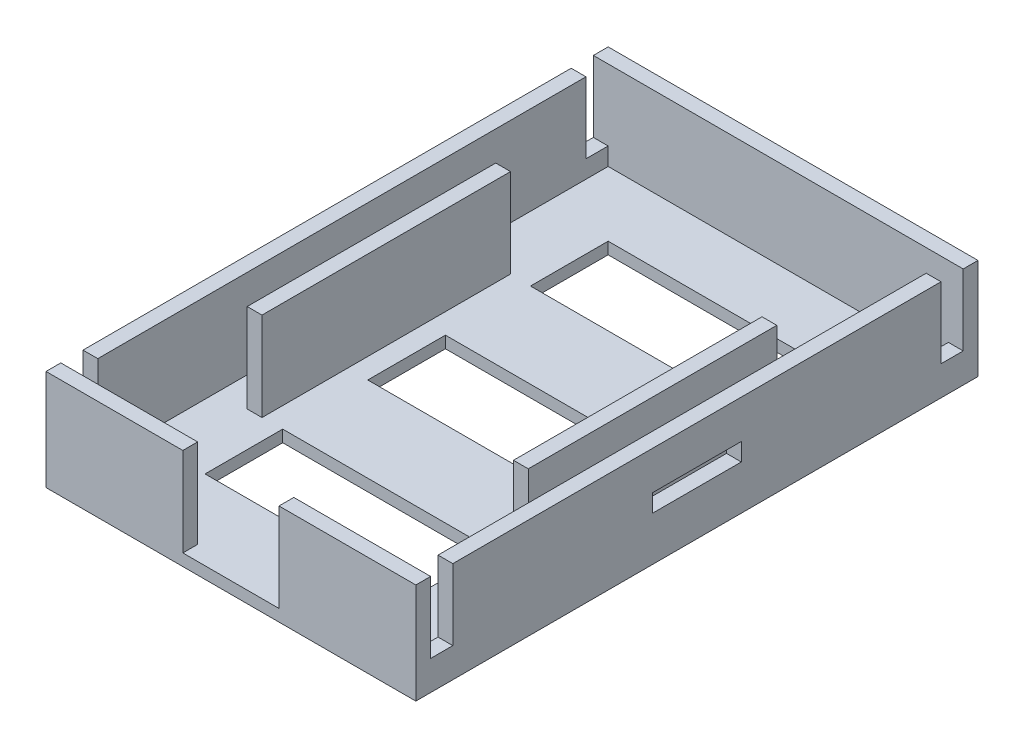
SolidWorks part; units mm, degrees
ref_plane "Front Plane" through (0, 0, 0) normal (0, 0, 1) x (1, 0, 0)
ref_plane "Top Plane" through (0, 0, 0) normal (0, 1, 0) x (1, 0, 0)
ref_plane "Right Plane" through (0, 0, 0) normal (1, 0, 0) x (0, 0, -1)
sketch "Sketch1" plane through (0, 0, 0) normal (0, 1, 0) x (1, 0, 0)
  line L1 (-12.5, -19) -> (12.5, -19)
  line L2 (-12.5, -19) -> (-12.5, 19)
  line L3 (-12.5, 19) -> (12.5, 19)
  line L4 (12.5, -19) -> (12.5, 19)
  line L5 (-12.5, -19) -> (12.5, 19) construction
  line L6 (-12.5, 19) -> (12.5, -19) construction
  point P0 (0, 0)
  dimension "D1" = 25
  dimension "D2" = 38
extrude "Boss-Extrude1" add sketch "Sketch1" along normal blind 6.8
sketch "Sketch2" plane through (0, 6.8, 0) normal (0, 1, 0) x (1, 0, 0)
  line L0 (-12.5, 19) -> (-12.5, -19) construction
  line L1 (-11.5, -18) -> (11.5, -18)
  line L2 (-11.5, -18) -> (-11.5, 18)
  line L3 (-11.5, 18) -> (11.5, 18)
  line L4 (11.5, -18) -> (11.5, 18)
  line L5 (-11.5, -18) -> (11.5, 18) construction
  line L6 (-11.5, 18) -> (11.5, -18) construction
  line L7 (-11.5, 18) -> (-12.5, 18)
  line L8 (-11.5, 18) -> (-11.5, 16.5)
  line L9 (-11.5, 16.5) -> (-12.5, 16.5)
  line L10 (-12.5, 18) -> (-12.5, 16.5)
  line L11 (0, -55) -> (0, 55) construction
  line L12 (11.5, 16.5) -> (12.5, 16.5)
  line L13 (12.5, 18) -> (12.5, 16.5)
  line L14 (11.5, 18) -> (12.5, 18)
  line L15 (-55, 0) -> (55, 0) construction
  line L16 (11.5, -16.5) -> (12.5, -16.5)
  line L17 (12.5, -18) -> (12.5, -16.5)
  line L18 (11.5, -18) -> (12.5, -18)
  line L19 (-11.5, -16.5) -> (-12.5, -16.5)
  line L20 (-12.5, -18) -> (-12.5, -16.5)
  line L21 (-11.5, -18) -> (-12.5, -18)
  point P0 (0, 0)
  line M5 (12.5, -19) -> (12.5, 19)
  line M7 (-12.5, 19) -> (-12.5, -19)
  dimension "D1" = 23
  dimension "D2" = 36
  dimension "D3" = 1.5
extrude "Cut-Extrude1" cut sketch "Sketch2" against normal blind 6 contours L1 L4 L3 L2 region at (0, 6.8, 0)
extrude "Cut-Extrude2" cut sketch "Sketch2<3>" against normal blind 4.8 contours L9 L2 L7 M7 | L14 L4 L12 M5 | L21 L2 L19 M7 | L4 L18 L16 M5 region at (-12, 6.8, 17.25) region at (12, 6.8, 17.25) region at (-12, 6.8, -17.25) region at (12, 6.8, -17.25)
sketch "Sketch2<3>" plane through (0, 6.8, 0) normal (0, 1, 0) x (1, 0, 0) same geometry as "Sketch2"
sketch "Sketch3" plane through (0, 0, 0) normal (1, 0, 0) x (0, 0, -1)
  line L0 (0, 0) -> (0, 6.8) construction
  line L1 (-16.5, 6.8) -> (16.5, 6.8) construction
  line L2 (-19, 0) -> (19, 0) construction
  line L3 (-3, 3) -> (3, 3)
  line L4 (-3, 3) -> (-3, 4.2)
  line L5 (-3, 4.2) -> (3, 4.2)
  line L6 (3, 3) -> (3, 4.2)
  line L7 (-3, 3) -> (3, 4.2) construction
  line L8 (-3, 4.2) -> (3, 3) construction
  point P5 (0, 3.6)
  dimension "D1" = 6
  dimension "D2" = 1.2
  dimension "D3" = 3
extrude "Cut-Extrude3" cut sketch "Sketch3" against normal through all both and the other way through all
sketch "Sketch4" plane through (0, 0.8, 0) normal (0, 1, 0) x (1, 0, 0)
  line L0 (0, 18) -> (0, -18) construction
  line L1 (-11.5, -18) -> (11.5, -18) construction
  line L2 (-12.5, -18) -> (12.5, -18) construction
  line L3 (-7.125, -13.625) -> (7.125, -13.625)
  line L4 (-7.125, -13.625) -> (-7.125, -8.375)
  line L5 (-7.125, -8.375) -> (7.125, -8.375)
  line L6 (7.125, -13.625) -> (7.125, -8.375)
  line L7 (-7.125, -13.625) -> (7.125, -8.375) construction
  line L8 (-7.125, -8.375) -> (7.125, -13.625) construction
  line L9 (-7.125, -2.625) -> (7.125, -2.625)
  line L10 (-7.125, -2.625) -> (-7.125, 2.625)
  line L11 (-7.125, 2.625) -> (7.125, 2.625)
  line L12 (7.125, -2.625) -> (7.125, 2.625)
  line L13 (-7.125, -2.625) -> (7.125, 2.625) construction
  line L14 (-7.125, 2.625) -> (7.125, -2.625) construction
  line L15 (-7.125, 8.375) -> (7.125, 8.375)
  line L16 (-7.125, 8.375) -> (-7.125, 13.625)
  line L17 (-7.125, 13.625) -> (7.125, 13.625)
  line L18 (7.125, 8.375) -> (7.125, 13.625)
  line L19 (-7.125, 8.375) -> (7.125, 13.625) construction
  line L20 (-7.125, 13.625) -> (7.125, 8.375) construction
  point P0 (0, -11)
  point P6 (0, 0)
  point P14 (0, 0)
  point P19 (0, 11)
  dimension "D1" = 7
  dimension "D2" = 14.25
  dimension "D3" = 5.25
  dimension "D5" = 5.75
  dimension "D4" = 3
extrude "Cut-Extrude4" cut sketch "Sketch4" against normal up to next and the other way through all
sketch "Sketch5" plane through (0, 0.8, 0) normal (0, 1, 0) x (1, 0, 0)
  line L0 (0, 18) -> (0, -18) construction
  line L1 (-11.5, -18) -> (11.5, -18) construction
  line L2 (-11.5, 0) -> (11.5, 0) construction
  line L3 (11.5, -16.5) -> (11.5, 16.5) construction
  line L4 (-11.5, -18) -> (-11.5, 18) construction
  line L5 (-9.5, 8.4) -> (-8.5, 8.4)
  line L6 (-9.5, 8.4) -> (-9.5, -8.4)
  line L7 (-9.5, -8.4) -> (-8.5, -8.4)
  line L8 (-8.5, 8.4) -> (-8.5, -8.4)
  line L9 (-9.5, 8.4) -> (-8.5, -8.4) construction
  line L10 (-9.5, -8.4) -> (-8.5, 8.4) construction
  line L11 (9.5, -8.4) -> (8.5, 8.4) construction
  line L12 (9.5, 8.4) -> (8.5, -8.4) construction
  line L13 (8.5, 8.4) -> (8.5, -8.4)
  line L14 (9.5, -8.4) -> (8.5, -8.4)
  line L15 (9.5, 8.4) -> (9.5, -8.4)
  line L16 (9.5, 8.4) -> (8.5, 8.4)
  point P0 (-9, 0)
  point P6 (0, 0)
  point P12 (0, 0)
  point P23 (9, 0)
  dimension "D1" = 1
  dimension "D2" = 2
  dimension "D3" = 16.8
extrude "Boss-Extrude2" add sketch "Sketch5" along normal up to surface (6 mm away) up to face at (-12, 6.8, 0)
sketch "Sketch6" plane through (0, 6.8, 0) normal (0, 1, 0) x (1, 0, 0)
  line L0 (0, -18) -> (0, -19) construction
  line L1 (-11.5, -18) -> (11.5, -18) construction
  line L2 (-12.5, -19) -> (12.5, -19) construction
  line L3 (-12.5, -18) -> (12.5, -18) construction
  line L4 (-3.25, -19) -> (3.25, -19)
  line L5 (-3.25, -19) -> (-3.25, -18)
  line L6 (-3.25, -18) -> (3.25, -18)
  line L7 (3.25, -19) -> (3.25, -18)
  line L8 (-3.25, -19) -> (3.25, -18) construction
  line L9 (-3.25, -18) -> (3.25, -19) construction
  point P6 (0, -18.5)
  dimension "D1" = 6.5
extrude "Cut-Extrude5" cut sketch "Sketch6" against normal up to surface (6 mm away) up to face at (0, 0.8, 0)
